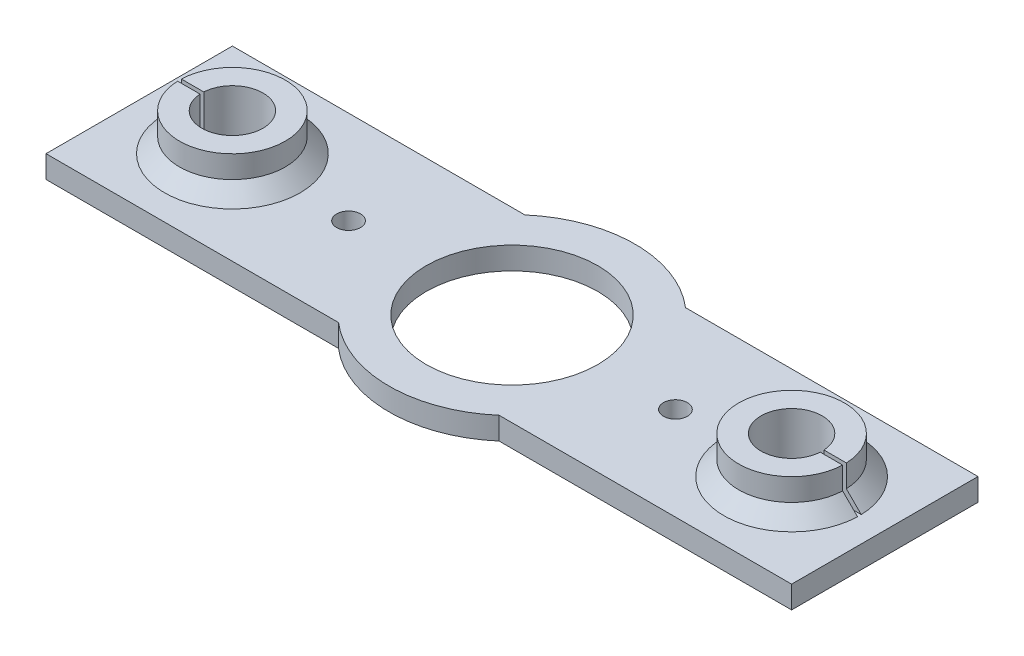
SolidWorks part; units mm, degrees
ref_plane "Front Plane" through (0, 0, 0) normal (0, 0, 1) x (1, 0, 0)
ref_plane "Top Plane" through (0, 0, 0) normal (0, 1, 0) x (1, 0, 0)
ref_plane "Right Plane" through (0, 0, 0) normal (1, 0, 0) x (0, 0, -1)
sketch "Sketch1" plane through (0, 0, 0) normal (0, 1, 0) x (1, 0, 0)
  line L0 (0, 18.2751) -> (0, -23.7638) construction
  line L1 (-40.7915, 0) -> (38.5461, 0) construction
  line L3 (50, -12.5) -> (-50, -12.5)
  line L4 (50, -12.5) -> (50, 12.5)
  line L5 (50, 12.5) -> (-50, 12.5)
  line L6 (-50, -12.5) -> (-50, 12.5)
  line L7 (50, -12.5) -> (-50, 12.5) construction
  line L8 (50, 12.5) -> (-50, -12.5) construction
  circle A0 centre (-37.5, 0) radius 4.1
  circle A1 centre (37.5, 0) radius 4.1
  circle A2 centre (-21.92, 0) radius 1.6
  circle A3 centre (21.92, 0) radius 1.6
  circle A4 centre (0, 0) radius 11.5
  circle A5 centre (0, 0) radius 16.5
  point P7 (0, 0)
  dimension "D1" = 8.2
  dimension "D2" = 75
  dimension "D5" = 3.2
  dimension "D6" = 43.84
  dimension "D7" = 23
  dimension "D8" = 5
  dimension "D3" = 25
  dimension "D4" = 100
extrude "Boss-Extrude1" add sketch "Sketch1" along normal blind 3 contours A5 L5 L6 L3 A0 A2 | L3 A5 L5 A4 | L5 A5 | A5 L3 L4 L5 A3 A1 | L3 A5 region at (32.1041, 0, 0) region at (0, 0, 14.1179) region at (0, 0, 12.086) region at (-32.1041, 0, 0) region at (0, 0, -14.1179)
sketch "Sketch2" plane through (0, 3, 0) normal (0, 1, 0) x (1, 0, 0)
  line L0 (0, 16.5) -> (0, -16.5) construction
  line L1 (0, 0) -> (-44.5975, 0) construction
  line L2 (-41.5899, 0.25) -> (-44.5931, 0.25)
  line L3 (-41.5899, -0.25) -> (-44.5931, -0.25)
  line L4 (41.5899, 0.25) -> (44.5931, 0.25)
  line L5 (41.5899, -0.25) -> (44.5931, -0.25)
  circle A0 centre (-37.5, 0) radius 4.0975
  circle A1 centre (-37.5, 0) radius 7.0975
  arc A2 (10.7703, 12.5) -> (-10.7703, 12.5) centre (0, 0) ccw construction
  arc A3 (-10.7703, -12.5) -> (10.7703, -12.5) centre (0, 0) ccw construction
  circle A4 centre (37.5, 0) radius 4.0975
  circle A5 centre (37.5, 0) radius 7.0975
  circle M13 centre (-37.5, 0) radius 4.1
  circle M17 centre (37.5, 0) radius 4.1
  dimension "D1" = 3
  dimension "D3" = 8.1951
  dimension "D2" = 0.5
extrude "Boss-Extrude2" add sketch "Sketch2" along normal blind 5 contours L3 A1 L2 M13 | A5 L5 L4 M17 region at (-43.0928, 3, -0.4507) region at (33.1993, 3, 0)
chamfer "Chamfer1" distance 2 angle 45 2 edges at (30.4025, 3, 0) (-30.4025, 3, 0)
